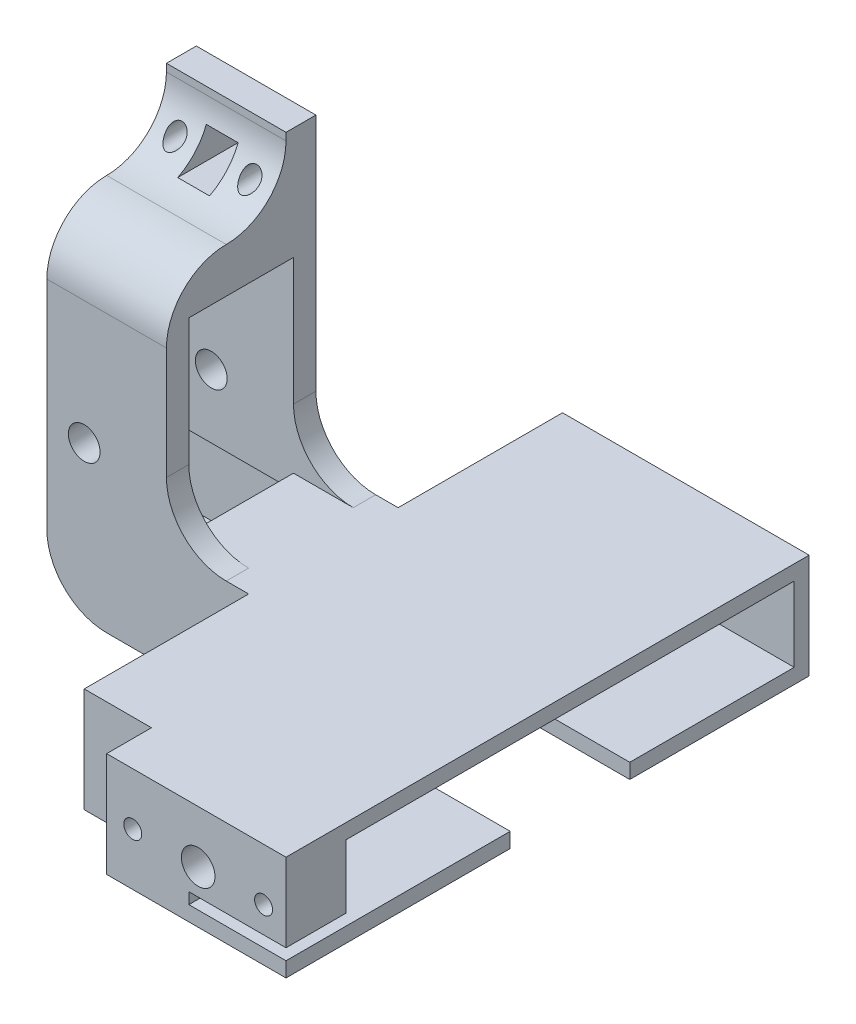
SolidWorks part; units mm, degrees
ref_plane "Front Plane" through (0, 0, 0) normal (0, 0, 1) x (1, 0, 0)
ref_plane "Top Plane" through (0, 0, 0) normal (0, 1, 0) x (1, 0, 0)
ref_plane "Right Plane" through (0, 0, 0) normal (1, 0, 0) x (0, 0, -1)
sketch "Sketch1" plane through (0, 0, 0) normal (0, 0, 1) x (1, 0, 0)
  line L4 (16, 54) -> (0, 54)
  line L5 (16, 54) -> (16, 14)
  line L7 (0, 54) -> (0, 0)
  line L8 (8, 54) -> (8, 0) construction
  line L9 (16, 14) -> (60, 14)
  line L11 (0, 0) -> (60, 0)
  line L12 (60, 14) -> (60, 0)
  line L14 (10.125, 45.875) -> (5.875, 45.875)
  line L15 (10.125, 45.875) -> (10.125, 50.125)
  line L16 (10.125, 50.125) -> (5.875, 50.125)
  line L17 (5.875, 45.875) -> (5.875, 50.125)
  circle A1 centre (5, 20.5) radius 2.125
  circle A2 centre (13, 48) radius 1.25
  circle A3 centre (3, 48) radius 1.25
  point P17 (10.125, 48)
  point P20 (8, 45.875)
  dimension "D4" = 4.25
  dimension "D8" = 2.5
  dimension "D9" = 2.5
  dimension "D12" = 4.25
  dimension "D1" = 16
  dimension "D2" = 40
  dimension "D3" = 6.5
  dimension "D5" = 60
  dimension "D6" = 14
  dimension "D7" = 5
  dimension "D10" = 10
  dimension "D11" = 6
extrude "Boss-Extrude1" add sketch "Sketch1" along normal blind 20
sketch "Sketch2" plane through (16, 0, 0) normal (1, 0, 0) x (0, 0, -1)
  line L0 (-10, 54) -> (-10, 0) construction
  line L1 (-3, 2) -> (-17, 2)
  line L2 (-3, 2) -> (-3, 39)
  line L3 (-3, 39) -> (-17, 39)
  line L4 (-17, 2) -> (-17, 39)
  line L5 (-20, 54) -> (0, 54) construction
  line L7 (-20, 0) -> (0, 0) construction
  line L8 (0, 14) -> (0, 54) construction
  line L9 (-20, 54) -> (-4, 54)
  line L10 (-20, 54) -> (-20, 45)
  line L11 (-20, 45) -> (-4, 45)
  line L12 (-4, 54) -> (-4, 45)
  point P9 (-10, 54)
  dimension "D1" = 15
  dimension "D2" = 14
  dimension "D3" = 2
  dimension "D4" = 4
  dimension "D5" = 9
extrude "Cut-Extrude1" cut sketch "Sketch2" against normal through all
sketch "Sketch3" plane through (0, 0, 0) normal (0, -1, 0) x (1, 0, 0)
  line L0 (27, 20) -> (27, 42)
  line L1 (0, 20) -> (60, 20) construction
  line L2 (27, 42) -> (60, 42)
  line L3 (60, 42) -> (60, 20)
  line L4 (27, 20) -> (60, 20)
  line L5 (60, 20) -> (60, 0) construction
  line L6 (60, 10) -> (0, 10) construction
  line L8 (27, 0) -> (27, -22)
  line L9 (27, -22) -> (60, -22)
  line L10 (60, -22) -> (60, 0)
  line L11 (27, 0) -> (60, 0)
  line L12 (0, 3) -> (0, 17) construction
  dimension "D1" = 22
  dimension "D2" = 33
extrude "Boss-Extrude2" add sketch "Sketch3" against normal up to surface (14 mm away) up to face at (30.6667, 14, 10)
sketch "Sketch4" plane through (60, 0, 0) normal (1, 0, 0) x (0, 0, -1)
  line L0 (-18, 0) -> (-18, 2)
  line L1 (-42, 0) -> (22, 0) construction
  line L2 (-18, 0) -> (-2, 0)
  line L3 (-2, 0) -> (-2, 2)
  line L4 (-20, 14) -> (-20, 45) construction
  line L5 (0, 14) -> (0, 54) construction
  line L6 (-2, 2) -> (20, 2)
  line L12 (-40, 2) -> (20, 2)
  line L13 (20, 2) -> (20, 12)
  line L14 (20, 12) -> (-40, 12)
  line L15 (-40, 12) -> (-40, 2)
  line L16 (-40, 2) -> (-18, 2)
  line L17 (20, 2) -> (20, 12)
  line L18 (20, 12) -> (-40, 12)
  line L19 (-40, 12) -> (-40, 2)
  dimension "D2" = 2
  dimension "D3" = 2
  dimension "D1" = 2
extrude "Cut-Extrude2" cut sketch "Sketch4" against normal offset from surface (31 mm away) 2 up to face at (27, 7, 31)
sketch "Sketch5" plane through (29, 0, 0) normal (1, 0, 0) x (0, 0, -1)
  line L0 (20, 12) -> (-40, 12) construction
  line L2 (-2, 2) -> (-2, 12)
  line L3 (-2, 12) -> (-18, 12)
  line L4 (-18, 2) -> (-18, 12)
  line L5 (-18, 2) -> (-18, 0) construction
  line L6 (-2, 2) -> (-18, 2)
extrude "Cut-Extrude3" cut sketch "Sketch5" against normal up to surface (29 mm away) up to face at (0, 20.5, 10)
sketch "Sketch7" plane through (0, 0, -20) normal (0, 0, 1) x (1, 0, 0)
  line L1 (27, 14) -> (27, 0) construction
  line L2 (27, 14) -> (60, 14) construction
  circle A0 centre (45, 7.3) radius 4
  dimension "D1" = 8
  dimension "D2" = 18
  dimension "D3" = 6.7
extrude "Cut-Extrude5" cut sketch "Sketch7" against normal up to surface (2 mm away) up to face at (43.5, 7, -22)
sketch "Sketch8" plane through (0, 0, 42) normal (0, 0, 1) x (1, 0, 0)
  line L0 (48.25, 14) -> (48.25, 0) construction
  line L1 (27, 14) -> (60, 14) construction
  line L2 (36, 14) -> (36, 0)
  line L4 (60, 14) -> (27, 14)
  line L5 (27, 14) -> (27, 0)
  line L6 (27, 0) -> (60, 0)
  line L7 (60, 0) -> (60, 14)
  line L8 (60, 14) -> (36, 14)
  line L10 (36, 0) -> (60, 0)
  line L11 (60, 0) -> (60, 14)
  circle A0 centre (57, 7) radius 1.2
  circle A1 centre (48.25, 7) radius 2.25
  circle A2 centre (39.5, 7) radius 1.2
  point P9 (60, 7)
  dimension "D3" = 2.4
  dimension "D5" = 4.5
  dimension "D2" = 3
  dimension "D4" = 8.75
  dimension "D6" = 24
  dimension "D1" = 0
extrude "Boss-Extrude3" add sketch "Sketch8" along normal blind 6
sketch "Sketch9" plane through (0, 0, 48) normal (0, 0, 1) x (1, 0, 0)
  line L0 (60, 0) -> (60, 14) construction
  line L1 (60, 2) -> (47, 2)
  line L2 (60, 2) -> (60, 3.5)
  line L3 (60, 3.5) -> (47, 3.5)
  line L4 (47, 2) -> (47, 3.5)
  line L5 (29, 2) -> (60, 2) construction
  circle A0 centre (57, 7) radius 1.2 construction
  circle A1 centre (48.25, 7) radius 2.25
  circle A2 centre (48.25, 7) radius 2.25
  circle A3 centre (39.5, 7) radius 1.2 construction
  circle A4 centre (57, 7) radius 1.2
  circle A5 centre (39.5, 7) radius 1.2
  dimension "D2" = 1.5
  dimension "D3" = 13
  dimension "D1" = 0
extrude "Cut-Extrude6" cut sketch "Sketch9" against normal up to surface (8 mm away) up to face at (44.5, 7, 40)
fillet "Fillet1" radius 8 5 edges at (0, 0, 10) (16, 14, 1.5) (16, 14, 18.5) (8, 45, 4) (8, 45, 20)
sketch "Sketch10" plane through (0, 0, 0) normal (0, 1, 0) x (1, 0, 0)
  line L0 (60, 22) -> (27, 22) construction
  line L1 (60, -46) -> (0, -46)
  line L2 (60, -46) -> (60, 22)
  line L3 (60, 22) -> (0, 22)
  line L4 (0, -46) -> (0, 22)
  line L5 (60, -48) -> (60, 22) construction
  line L7 (0, -4) -> (0, -12) construction
  line L8 (60, -48) -> (36, -48) construction
  dimension "D1" = 2
extrude "Short Cut 1" [suppressed] cut sketch "Sketch10" along normal through all
